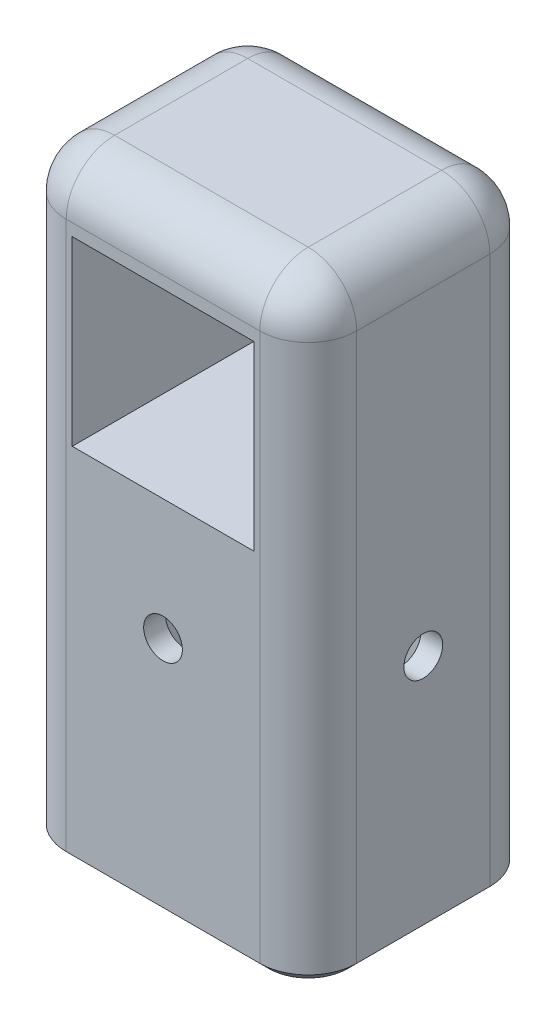
SolidWorks part; units mm, degrees
ref_plane "Front Plane" through (0, 0, 0) normal (0, 0, 1) x (1, 0, 0)
ref_plane "Top Plane" through (0, 0, 0) normal (0, 1, 0) x (1, 0, 0)
ref_plane "Right Plane" through (0, 0, 0) normal (1, 0, 0) x (0, 0, -1)
sketch "Sketch1" plane through (0, 0, 0) normal (0, 1, 0) x (1, 0, 0)
  line L1 (0, 0) -> (24, 0)
  line L2 (0, 0) -> (0, 19)
  line L3 (0, 19) -> (24, 19)
  line L4 (24, 0) -> (24, 19)
  dimension "D1" = 24
  dimension "D2" = 19
extrude "Boss-Extrude1" add sketch "Sketch1" along normal blind 50
sketch "Sketch2" plane through (0, 0, 0) normal (0, 0, 1) x (1, 0, 0)
  line L0 (0, 0) -> (24, 0) construction
  line L1 (4.5, 45) -> (19.5, 45)
  line L2 (4.5, 45) -> (4.5, 30)
  line L3 (4.5, 30) -> (19.5, 30)
  line L4 (19.5, 45) -> (19.5, 30)
  line L5 (0, 50) -> (24, 50) construction
  point P6 (12, 45)
  point P9 (12, 50)
  dimension "D1" = 15
  dimension "D2" = 30
extrude "Cut-Extrude1" cut sketch "Sketch2" against normal blind 16
sketch "Sketch3" plane through (0, 0, -16) normal (0, 0, 1) x (1, 0, 0)
  line L0 (19.5, 45) -> (4.5, 45) construction
  line L1 (19.5, 30) -> (19.5, 45) construction
  circle A0 centre (12, 37.5) radius 1.6
  point P5 (12, 45)
  point P9 (19.5, 37.5)
  dimension "D1" = 3.2
extrude "Cut-Extrude2" cut sketch "Sketch3" against normal up to next
sketch "Sketch4" plane through (0, 0, 0) normal (0, -1, 0) x (1, 0, 0)
  line L5 (0, 0) -> (24, 0) construction
  line L11 (24, 0) -> (24, -19) construction
  line L48 (24, -19) -> (0, -19) construction
  line L49 (9.05, -17.2) -> (14.95, -17.2)
  line L50 (9.05, -17.2) -> (9.05, -14.2)
  line L51 (9.05, -14.2) -> (14.95, -14.2)
  line L52 (14.95, -17.2) -> (14.95, -14.2)
  line L53 (1.8, -12.45) -> (4.8, -12.45)
  line L54 (1.8, -12.45) -> (1.8, -6.55)
  line L55 (1.8, -6.55) -> (4.8, -6.55)
  line L56 (4.8, -12.45) -> (4.8, -6.55)
  line L57 (9.05, -4.8) -> (14.95, -4.8)
  line L58 (9.05, -4.8) -> (9.05, -1.8)
  line L59 (9.05, -1.8) -> (14.95, -1.8)
  line L60 (14.95, -4.8) -> (14.95, -1.8)
  line L61 (19.2, -12.45) -> (22.2, -12.45)
  line L62 (19.2, -12.45) -> (19.2, -6.55)
  line L63 (19.2, -6.55) -> (22.2, -6.55)
  line L64 (22.2, -12.45) -> (22.2, -6.55)
  line L65 (0, -19) -> (0, 0) construction
  point P20 (12, -17.2)
  point P21 (12, -4.8)
  point P24 (12, -19)
  point P25 (1.8, -9.5)
  point P26 (19.2, -9.5)
  point P37 (24, -9.5)
  dimension "D1" = 5.9
  dimension "D2" = 3
  dimension "D3" = 1.8
  dimension "D4" = 1.8
  dimension "D5" = 1.8
  dimension "D6" = 1.8
extrude "Cut-Extrude3" cut sketch "Sketch4" against normal blind 23
sketch "Sketch5" plane through (0, 0, -19) normal (0, 0, -1) x (-1, 0, 0)
  line L0 (-24, 0) -> (0, 0) construction
  circle A0 centre (-12, 20) radius 1.6
  point P5 (-12, 0)
  dimension "D1" = 3.2
  dimension "D2" = 20
extrude "Cut-Extrude4" cut sketch "Sketch5" against normal through all
sketch "Sketch6" plane through (0, 0, 0) normal (-1, 0, 0) x (0, 0, 1)
  line L0 (-19, 0) -> (0, 0) construction
  circle A0 centre (-9.5, 20) radius 1.6
  point P5 (-9.5, 0)
  dimension "D1" = 3.2
  dimension "D2" = 20
extrude "Cut-Extrude5" cut sketch "Sketch6" against normal through all
fillet "Fillet4" radius 4 4 edges at (24, 25, -19) (0, 25, -19) (24, 25, 0) (0, 25, 0)
fillet "Fillet5" radius 4 8 edges at (12, 50, 0) (22.8284, 50, -1.1716) (24, 50, -9.5) (22.8284, 50, -17.8284) (12, 50, -19) (1.1716, 50, -17.8284) (1.1716, 50, -1.1716) (0, 50, -9.5)
chamfer "Chamfer1" distance 0.75 angle 45 24 edges at (12, 0, 0) (22.8284, 0, -1.1716) (1.1716, 0, -1.1716) (24, 0, -9.5) (0, 0, -9.5) (22.8284, 0, -17.8284) (1.1716, 0, -17.8284) (12, 0, -19) (20.7, 0, -12.45) (22.2, 0, -9.5) (20.7, 0, -6.55) (19.2, 0, -9.5) (12, 0, -4.8) (14.95, 0, -3.3) (12, 0, -1.8) (9.05, 0, -3.3) (3.3, 0, -12.45) (4.8, 0, -9.5) (3.3, 0, -6.55) (1.8, 0, -9.5) (12, 0, -17.2) (14.95, 0, -15.7) (12, 0, -14.2) (9.05, 0, -15.7)
